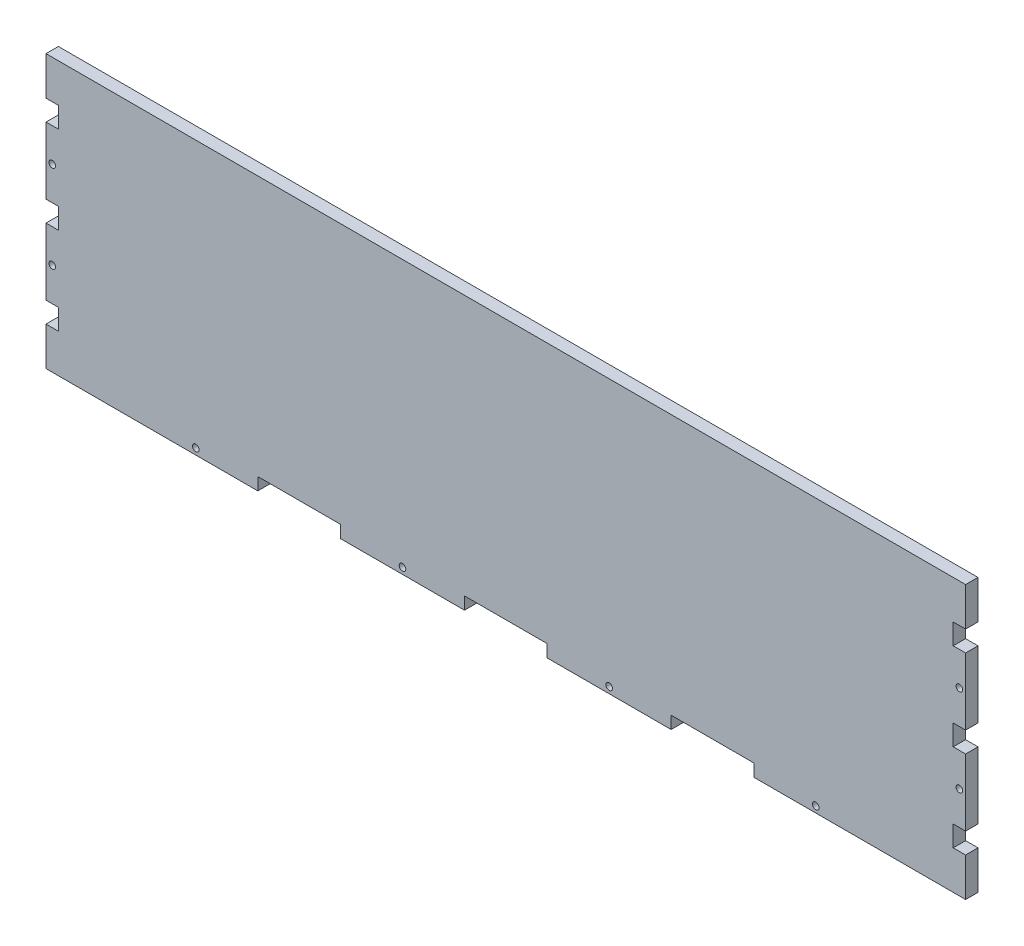
SolidWorks part; units mm, degrees
ref_plane "Front Plane" through (0, 0, 0) normal (0, 0, 1) x (1, 0, 0)
ref_plane "Top Plane" through (0, 0, 0) normal (0, 1, 0) x (1, 0, 0)
ref_plane "Right Plane" through (0, 0, 0) normal (1, 0, 0) x (0, 0, -1)
sketch "Sketch1" plane through (0, 0, 0) normal (0, 0, 1) x (1, 0, 0)
  line L1 (-222.5, -66) -> (222.5, -66)
  line L2 (-222.5, -66) -> (-222.5, 66)
  line L3 (-222.5, 66) -> (222.5, 66)
  line L4 (222.5, -66) -> (222.5, 66)
  line L5 (-222.5, -66) -> (222.5, 66) construction
  line L6 (-222.5, 66) -> (222.5, -66) construction
  point P0 (0, 0)
  dimension "D1" = 445
  dimension "D2" = 132
extrude "Boss-Extrude1" add sketch "Sketch1" along normal blind 6
sketch "Sketch2" plane through (0, 0, 0) normal (0, 0, -1) x (-1, 0, 0)
  line L0 (222.5, 47.3321) -> (222.5, 37.3321) construction
  line L1 (222.5, 37.3321) -> (216.5, 37.3321) construction
  line L2 (216.5, 37.3321) -> (216.5, 47.3321) construction
  line L3 (216.5, 47.3321) -> (222.5, 47.3321) construction
  line L12 (222.5, -37.3321) -> (222.5, -47.3321) construction
  line L13 (222.5, -47.3321) -> (216.5, -47.3321) construction
  line L14 (216.5, -47.3321) -> (216.5, -37.3321) construction
  line L15 (216.5, -37.3321) -> (222.5, -37.3321) construction
  line L16 (222.5, 47.3321) -> (222.5, 37.3321)
  line L17 (222.5, 37.3321) -> (216.5, 37.3321)
  line L18 (216.5, 37.3321) -> (216.5, 47.3321)
  line L19 (216.5, 47.3321) -> (222.5, 47.3321)
  line L20 (222.5, -37.3321) -> (222.5, -47.3321)
  line L21 (222.5, -47.3321) -> (216.5, -47.3321)
  line L22 (216.5, -47.3321) -> (216.5, -37.3321)
  line L23 (216.5, -37.3321) -> (222.5, -37.3321)
  line L24 (-216.5, -37.3321) -> (-216.5, -47.3321) construction
  line L25 (-216.5, -47.3321) -> (-222.5, -47.3321) construction
  line L26 (-222.5, -47.3321) -> (-222.5, -37.3321) construction
  line L27 (-222.5, -37.3321) -> (-216.5, -37.3321) construction
  line L28 (-216.5, 47.3321) -> (-216.5, 37.3321) construction
  line L29 (-216.5, 37.3321) -> (-222.5, 37.3321) construction
  line L30 (-222.5, 37.3321) -> (-222.5, 47.3321) construction
  line L31 (-222.5, 47.3321) -> (-216.5, 47.3321) construction
  line L32 (-216.5, -37.3321) -> (-216.5, -47.3321)
  line L33 (-216.5, -47.3321) -> (-222.5, -47.3321)
  line L34 (-222.5, -47.3321) -> (-222.5, -37.3321)
  line L35 (-222.5, -37.3321) -> (-216.5, -37.3321)
  line L36 (-216.5, 47.3321) -> (-216.5, 37.3321)
  line L37 (-216.5, 37.3321) -> (-222.5, 37.3321)
  line L38 (-222.5, 37.3321) -> (-222.5, 47.3321)
  line L39 (-222.5, 47.3321) -> (-216.5, 47.3321)
  line L44 (222.5, -5) -> (222.5, 5)
  line L45 (216.5, -5) -> (222.5, -5)
  line L46 (216.5, 5) -> (216.5, -5)
  line L47 (222.5, 5) -> (216.5, 5)
  line L48 (222.5, -5) -> (222.5, 5)
  line L49 (216.5, -5) -> (222.5, -5)
  line L50 (216.5, 5) -> (216.5, -5)
  line L51 (222.5, 5) -> (216.5, 5)
  line L52 (-216.5, -5) -> (-216.5, 5)
  line L53 (-222.5, -5) -> (-216.5, -5)
  line L54 (-222.5, 5) -> (-222.5, -5)
  line L55 (-216.5, 5) -> (-222.5, 5)
  line L56 (-216.5, -5) -> (-216.5, 5)
  line L57 (-222.5, -5) -> (-216.5, -5)
  line L58 (-222.5, 5) -> (-222.5, -5)
  line L59 (-216.5, 5) -> (-222.5, 5)
  circle A0 centre (219.5, 21.1661) radius 1.6 construction
  circle A1 centre (219.5, -21.1661) radius 1.6 construction
  circle A2 centre (-219.5, 21.1661) radius 1.6 construction
  circle A3 centre (-219.5, -21.1661) radius 1.6 construction
  circle A4 centre (219.5, 21.1661) radius 1.6
  circle A5 centre (219.5, -21.1661) radius 1.6
  circle A6 centre (-219.5, 21.1661) radius 1.6
  circle A7 centre (-219.5, -21.1661) radius 1.6
  dimension "D2" = 0
  dimension "D3" = 0
extrude "Cut-Extrude1" cut sketch "Sketch2" against normal up to next
sketch "Sketch3" plane through (0, 0, 0) normal (0, 0, -1) x (-1, 0, 0)
  circle A0 centre (-150, -63) radius 1.6 construction
  circle A1 centre (-50, -63) radius 1.6 construction
  circle A2 centre (50, -63) radius 1.6 construction
  circle A3 centre (150, -63) radius 1.6 construction
  circle A4 centre (-150, -63) radius 1.6
  circle A5 centre (-50, -63) radius 1.6
  circle A6 centre (50, -63) radius 1.6
  circle A7 centre (150, -63) radius 1.6
extrude "Cut-Extrude2" cut sketch "Sketch3" against normal up to next
sketch "Sketch4" plane through (0, 0, 0) normal (0, 0, -1) x (-1, 0, 0)
  line L0 (80, -66) -> (120, -66) construction
  line L1 (120, -66) -> (120, -60) construction
  line L2 (120, -60) -> (80, -60) construction
  line L3 (80, -60) -> (80, -66) construction
  line L4 (-20, -66) -> (20, -66) construction
  line L5 (20, -66) -> (20, -60) construction
  line L6 (20, -60) -> (-20, -60) construction
  line L7 (-20, -60) -> (-20, -66) construction
  line L8 (-120, -66) -> (-80, -66) construction
  line L9 (-80, -66) -> (-80, -60) construction
  line L10 (-80, -60) -> (-120, -60) construction
  line L11 (-120, -60) -> (-120, -66) construction
  line L12 (80, -66) -> (120, -66)
  line L13 (120, -66) -> (120, -60)
  line L14 (120, -60) -> (80, -60)
  line L15 (80, -60) -> (80, -66)
  line L16 (-20, -66) -> (20, -66)
  line L17 (20, -66) -> (20, -60)
  line L18 (20, -60) -> (-20, -60)
  line L19 (-20, -60) -> (-20, -66)
  line L20 (-120, -66) -> (-80, -66)
  line L21 (-80, -66) -> (-80, -60)
  line L22 (-80, -60) -> (-120, -60)
  line L23 (-120, -60) -> (-120, -66)
extrude "Cut-Extrude3" cut sketch "Sketch4" against normal up to next
